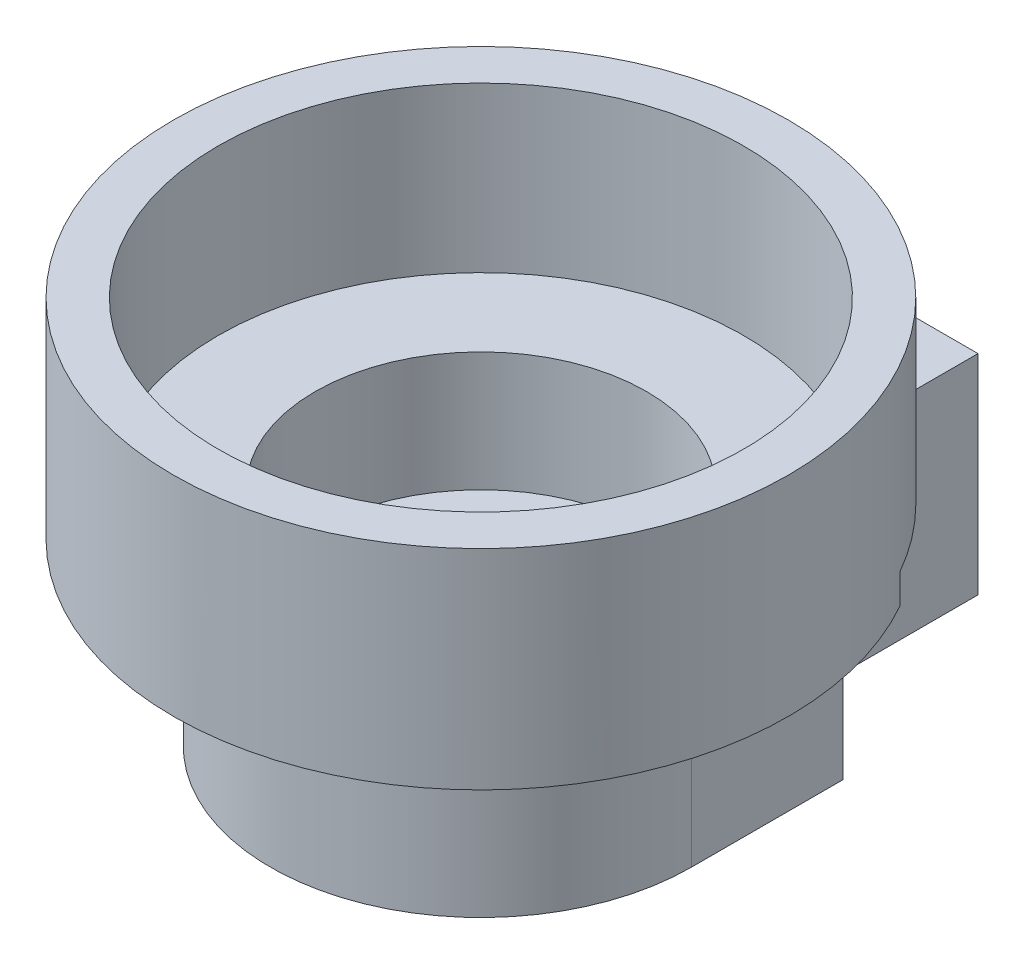
SolidWorks part; units mm, degrees
ref_plane "Front Plane" through (0, 0, 0) normal (0, 0, 1) x (1, 0, 0)
ref_plane "Top Plane" through (0, 0, 0) normal (0, 1, 0) x (1, 0, 0)
ref_plane "Right Plane" through (0, 0, 0) normal (1, 0, 0) x (0, 0, -1)
sketch "Sketch1" plane through (0, 0, 0) normal (0, 0, 1) x (1, 0, 0)
  line L0 (0, 0) -> (-14.1, 0)
  line L1 (-14.1, 0) -> (-14.1, 12)
  line L2 (-14.1, 12) -> (-20.6, 12)
  line L3 (-20.6, 12) -> (-20.6, 26)
  line L4 (-20.6, 26) -> (-17.6, 26)
  line L5 (-17.6, 26) -> (-17.6, 15)
  line L6 (-17.6, 15) -> (-11.1, 15)
  line L7 (-11.1, 15) -> (-11.1, 7)
  line L8 (-11.1, 7) -> (0, 7)
  line L9 (0, 7) -> (0, 0)
  point P11 (0, 0)
  point P12 (-18.6206, 0.1605)
  dimension "D1" = 7
  dimension "D2" = 8
  dimension "D3" = 11.1
  dimension "D4" = 11
  dimension "D5" = 17.6
  dimension "D6" = 3
  dimension "D7" = 3
  dimension "D8" = 3
revolve "Revolve1" add sketch "Sketch1" angle 360 about L9
sketch "Sketch2" plane through (0, 0, 0) normal (0, -1, 0) x (1, 0, 0)
  circle A0 centre (0, 0) radius 4.15
  dimension "D1" = 8.3
extrude "Cut-Extrude1" cut sketch "Sketch2" against normal through all
sketch "Sketch3" plane through (0, 12, 0) normal (0, -1, 0) x (1, 0, 0)
  line L0 (-14.1, 0) -> (-14.1, -25.4)
  line L1 (-14.1, -25.4) -> (14.1, -25.4)
  line L2 (14.1, -25.4) -> (14.1, 0)
  circle A0 centre (0, 0) radius 14.1 construction
  arc A1 (-14.1, 0) -> (14.1, 0) centre (0, 0) ccw
  dimension "D1" = 25.4
extrude "Boss-Extrude1" add sketch "Sketch3" along normal up to surface (12 mm away) up to face at (0, 0, -4.15)
sketch "Sketch4" plane through (0, 0, 0) normal (0, -1, 0) x (1, 0, 0)
  circle A0 centre (0, -18.1) radius 4.625
  point P4 (0, 0)
  dimension "D1" = 9.25
  dimension "D2" = 18.1
extrude "Cut-Extrude2" cut sketch "Sketch4" against normal blind 10.62
sketch "Sketch5" plane through (-14.1, 0, 0) normal (-1, 0, 0) x (0, 0, 1)
  line L0 (0, 0) -> (-25.4, 0) construction
  circle A0 centre (-18.1, 6) radius 2
  dimension "D2" = 4
  dimension "D1" = 6
  dimension "D3" = 18.1
extrude "Cut-Extrude3" cut sketch "Sketch5" against normal blind 22.86
sketch "Sketch6" plane through (0, 12, 0) normal (0, 1, 0) x (1, 0, 0)
  line L3 (14.1, 15.0183) -> (14.1, 25.4)
  line L4 (14.1, 25.4) -> (-14.1, 25.4)
  line L5 (-14.1, 25.4) -> (-14.1, 15.0183)
  line L6 (14.1, 15.0183) -> (14.1, 25.4)
  line L7 (14.1, 25.4) -> (-14.1, 25.4)
  line L8 (-14.1, 25.4) -> (-14.1, 15.0183)
  arc A1 (14.1, 15.0183) -> (-14.1, 15.0183) centre (0, 0) ccw
  arc A2 (14.1, 15.0183) -> (-14.1, 15.0183) centre (0, 0) ccw
  dimension "D1" = 0
extrude "Boss-Extrude2" add sketch "Sketch6" along normal blind 2
ref_plane "Plane1" through (-20.6, 0, 0) normal (-1, 0, 0) x (0, 0, 1)
sketch "Sketch7" plane through (-20.6, 0, 0) normal (-1, 0, 0) x (0, 0, 1)
  line L1 (0, 0) -> (-25.4, 0) construction
  line L2 (-10.16, 0) -> (-10.16, 14)
  line L6 (-25.4, 0) -> (0, 0)
  line L7 (0, 0) -> (0, 12)
  line L8 (0, 12) -> (-15.0183, 12)
  line L9 (-15.0183, 12) -> (-15.0183, 14)
  line L10 (-15.0183, 14) -> (-25.4, 14)
  line L11 (-25.4, 14) -> (-25.4, 0)
  line L12 (-25.4, 0) -> (-10.16, 0)
  line L16 (-10.16, 14) -> (-25.4, 14)
  line L17 (-25.4, 14) -> (-25.4, 0)
  point P2 (-10.9071, 0)
  point P10 (-10.16, 14)
  point P15 (-10.16, 12)
  dimension "D2" = 15.24
  dimension "D1" = 0
extrude "Cut-Extrude4" cut sketch "Sketch7" against normal blind 12.7
mirror "Mirror1" about plane through (0, 0, 0) normal (1, 0, 0) of "Cut-Extrude4"
